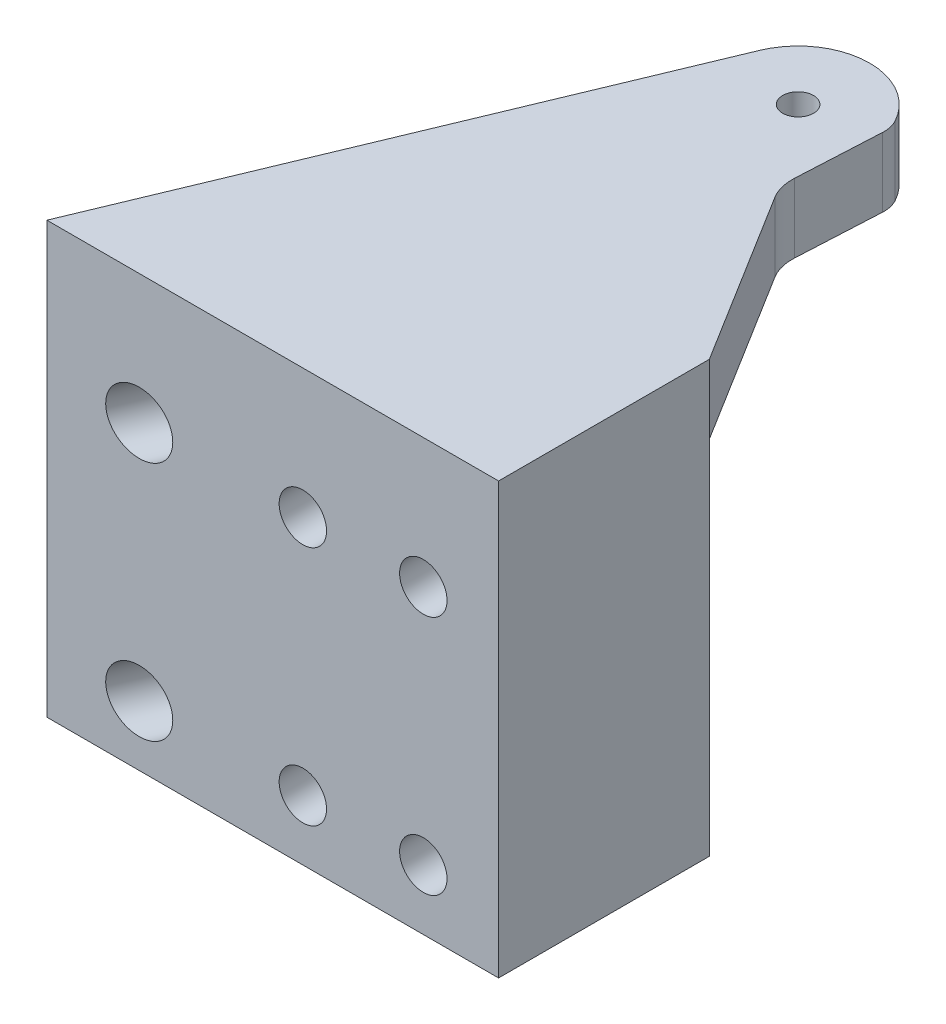
SolidWorks part; units mm, degrees
ref_plane "Front Plane" through (0, 0, 0) normal (0, 0, 1) x (1, 0, 0)
ref_plane "Top Plane" through (0, 0, 0) normal (0, 1, 0) x (1, 0, 0)
ref_plane "Right Plane" through (0, 0, 0) normal (1, 0, 0) x (0, 0, -1)
sketch "Sketch2" plane through (0, 0, 0) normal (0, 1, 0) x (1, 0, 0)
  line L0 (0, 0) -> (0, -15.6292)
  line L1 (0, -15.6292) -> (36.8202, -15.6292) construction
  line L2 (36.8202, -15.6292) -> (0, 0)
  line L5 (0, -15.6292) -> (0, -43.6292)
  line L6 (0, -43.6292) -> (36.8202, -43.6292)
  line L7 (36.8202, -15.6292) -> (36.8202, -43.6292)
  line L8 (18.4101, -43.6292) -> (18.4101, -15.6292) construction
  line L9 (0, -29.6292) -> (36.8202, -29.6292) construction
  point P282 (18.4101, -29.6292)
  dimension "D1" = 40
  dimension "D2" = 23
  dimension "D3" = 28
extrude "Boss-Extrude1" add sketch "Sketch2" along normal blind 48
sketch "Sketch4" plane through (0, 0, 43.6292) normal (0, 0, 1) x (1, 0, 0)
  line L0 (0, 48) -> (36.8202, 48) construction
  line L1 (10.8202, 40) -> (26.8202, 40) construction
  line L2 (10.8202, 40) -> (10.8202, 8) construction
  line L3 (10.8202, 8) -> (26.8202, 8) construction
  line L4 (26.8202, 40) -> (26.8202, 8) construction
  line L5 (18.8202, 8) -> (18.8202, 40) construction
  line L6 (10.8202, 24) -> (26.8202, 24) construction
  line L7 (36.8202, 48) -> (36.8202, 0) construction
  circle A0 centre (10.8202, 40) radius 3.15
  circle A1 centre (26.8202, 40) radius 3.15
  circle A2 centre (10.8202, 8) radius 3.15
  circle A3 centre (26.8202, 8) radius 3.15
  circle A4 centre (10.8202, 40) radius 2
  circle A5 centre (26.8202, 40) radius 2
  circle A6 centre (10.8202, 8) radius 2
  circle A7 centre (26.8202, 8) radius 2
  point P197 (18.8202, 24)
  dimension "D1" = 6.3
  dimension "D2" = 6.3
  dimension "D3" = 6.3
  dimension "D4" = 6.3
  dimension "D9" = 4
  dimension "D10" = 4
  dimension "D11" = 4
  dimension "D12" = 4
  dimension "D5" = 16
  dimension "D6" = 32
  dimension "D7" = 8
  dimension "D8" = 10
extrude "Cut-Extrude2" cut sketch "Sketch4" against normal blind 4.7 contours A4 | A0 A4 | A1 A5 | A5 | A7 | A3 A7 | A6 | A2 A6 region at (7.7593, 40, 43.6292) region at (23.7593, 40, 43.6292) region at (7.7593, 8, 43.6292) region at (23.7593, 8, 43.6292) region at (10.8202, 40, 43.6292) region at (26.8202, 40, 43.6292) region at (10.8202, 8, 43.6292) region at (26.8202, 8, 43.6292)
sketch "Sketch6" plane through (0, 0, 0) normal (0, -1, 0) x (1, 0, 0)
  line L0 (36.8202, 15.6292) -> (22.2793, -22.9412)
  line L1 (0, 0) -> (4.0568, -21.3624)
  line L2 (4.0568, -21.3624) -> (0, 0)
  line L3 (36.8202, 43.6292) -> (0, 43.6292)
  line L4 (0, 0) -> (36.8202, 15.6292)
  line L5 (36.8202, 15.6292) -> (36.8202, 43.6292)
  line L6 (36.8202, 43.6292) -> (0, 43.6292)
  line L7 (0, 43.6292) -> (0, 0)
  line L9 (36.8202, 15.6292) -> (36.8202, 43.6292)
  line L10 (36.8202, 43.6292) -> (0, 43.6292)
  line L12 (22.2793, -22.9412) -> (21.5556, -8.9412)
  line L13 (21.5556, -8.9412) -> (36.8202, 15.6292)
  line L14 (0, 0) -> (-23.1798, 43.6292)
  line L15 (36.8202, 43.6292) -> (-23.1798, 43.6292)
  line L16 (-23.1798, 43.6292) -> (4.6178, -23.2368)
  line L17 (0, 0) -> (-4.2396, -1.9306)
  circle A0 centre (13.39, -19.59) radius 2.05
  arc A1 (4.0568, -21.3624) -> (22.2793, -22.9412) centre (13.39, -19.59) ccw
  line M5 (0, 0) -> (36.8202, 15.6292)
  line M6 (36.8202, 15.6292) -> (36.8202, 43.6292)
  line M7 (36.8202, 43.6292) -> (0, 43.6292)
  line M8 (0, 43.6292) -> (0, 0)
  dimension "D4" = 19
  dimension "4.1" = 4.1
  dimension "D2" = 13.39
  dimension "D3" = 19.59
  dimension "D5" = 14
  dimension "D6" = 60
  dimension "D1" = 0
extrude "Boss-Extrude3" add sketch "Sketch6" against normal blind 9.18 from surface contours L1 A1 L12 L13 A0 M5 | L3 L2 M8 | M8 M5 M6 M7 | A1 L1 L14 | L17 L14 L16 region at (15.0842, 0, -7.6218) region at (17.0711, 0, 25.4377) region at (-7.7266, 0, 29.0862) region at (-9.1398, 0, 13.8996) region at (0.003, 0, -8.0956) starting at face at (18.4101, 48, 25.7219)
extrude "Cut-Extrude3" cut sketch "Sketch4<3>" against normal blind 8 contours A4 | A5 | A7 | A6 region at (10.8202, 40, 43.6292) region at (26.8202, 40, 43.6292) region at (10.8202, 8, 43.6292) region at (26.8202, 8, 43.6292)
sketch "Sketch4<3>" plane through (0, 0, 43.6292) normal (0, 0, 1) x (1, 0, 0) same geometry as "Sketch4"
fillet "Fillet3" radius 4 1 edges at (22.2793, 52.59, -22.9412)
fillet "Fillet4" radius 6 1 edges at (21.5556, 52.59, -8.9412)
extrude "Boss-Extrude4" add sketch "Sketch6<4>" along normal up to surface from surface contours L15 L14 M8 | L17 L14 L16 region at (-7.7266, 0, 29.0862) region at (-9.1398, 0, 13.8996) up to face at (18.4101, 0, 25.7219) starting at face at (13.39, 48, -17.54)
sketch "Sketch6<4>" plane through (0, 0, 0) normal (0, -1, 0) x (1, 0, 0) same geometry as "Sketch6"
sketch "Sketch3" plane through (0, 0, 0) normal (0.3907, 0, -0.9205) x (-0.9205, 0, -0.3907)
  line L0 (-7, 40) -> (-7, 8) construction
  circle A0 centre (-7, 40) radius 4.1
  circle A1 centre (-7, 8) radius 4.1
  circle A2 centre (-7, 40) radius 2.05
  circle A3 centre (-7, 8) radius 2.05
  dimension "D2" = 8.2
  dimension "D3" = 4.1
  dimension "D5" = 4.1
  dimension "D1" = 32
extrude "Cut-Extrude6" cut sketch "Sketch3" against normal blind 66 from offset 5 contours A2 | A2 A0 | A3 | A1 A3 region at (10.1109, 40, 4.2918) region at (10.1109, 8, 4.2918) region at (6.4435, 40, 2.7351) region at (6.4435, 8, 2.7351) offset against normal yes
extrude "Cut-Extrude7" cut sketch "Sketch3<3>" against normal blind 7 contours A2 | A3 region at (6.4435, 40, 2.7351) region at (6.4435, 8, 2.7351)
sketch "Sketch3<3>" plane through (0, 0, 0) normal (0.3907, 0, -0.9205) x (-0.9205, 0, -0.3907) same geometry as "Sketch3"
